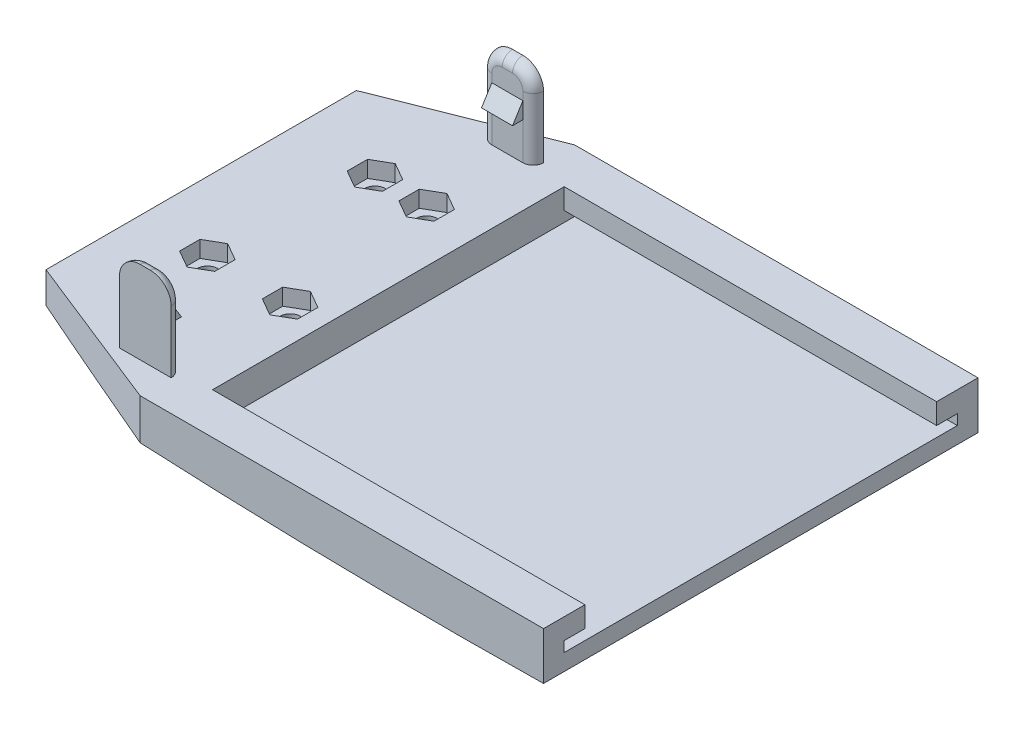
SolidWorks part; units mm, degrees
material "1060 Alloy"
ref_plane "Front Plane" through (0, 0, 0) normal (0, 0, 1) x (1, 0, 0)
ref_plane "Top Plane" through (0, 0, 0) normal (0, 1, 0) x (1, 0, 0)
ref_plane "Right Plane" through (0, 0, 0) normal (1, 0, 0) x (0, 0, -1)
sketch "Sketch1" plane through (0, 0, 0) normal (0, 1, 0) x (1, 0, 0)
  line L1 (0, 0) -> (270.5, 0)
  line L2 (0, 0) -> (0, 210)
  line L3 (0, 210) -> (270.5, 210)
  line L4 (270.5, 0) -> (270.5, 210)
  dimension "D1" = 270.5
  dimension "D2" = 210
extrude "Boss-Extrude1" add sketch "Sketch1" along normal blind 15
sketch "Sketch5" plane through (0, 15, 0) normal (0, 1, 0) x (1, 0, 0)
  line L0 (0, 105) -> (90.5, 105) construction
  line L1 (0, 210) -> (0, 0) construction
  line L3 (33, 105) -> (33, 75) construction
  line L4 (40, 105) -> (40, 149) construction
  line L5 (65, 105) -> (65, 149) construction
  line L6 (73, 105) -> (73, 75) construction
  circle A1 centre (33, 75) radius 5
  circle A2 centre (40, 149) radius 5
  circle A3 centre (65, 149) radius 5
  circle A4 centre (73, 75) radius 5
  dimension "D1" = 33
  dimension "D9" = 10
  dimension "D10" = 10
  dimension "D11" = 10
  dimension "D12" = 10
  dimension "D2" = 30
  dimension "D3" = 40
  dimension "D4" = 44
  dimension "D5" = 65
  dimension "D6" = 44
  dimension "D7" = 73
  dimension "D8" = 30
ref_plane "Plane1" through (0, 0, -150) normal (0, 0, 1) x (1, 0, 0)
sketch "Sketch12" plane through (0, 0, -150) normal (0, 0, 1) x (1, 0, 0)
  line L3 (0, 0) -> (270.5, 0) construction
  line L5 (270.5, 0) -> (270.5, -7.9767)
  line L11 (0, 0) -> (270.5, 0)
  arc A10 (0, 0) -> (270.5, -7.9767) centre (222.5, 2954.7793) ccw
  dimension "D1" = 270.5
extrude "Boss-Extrude5" add sketch "Sketch12" along normal blind 150 and the other way blind 60
extrude "Cut-Extrude7" cut sketch "Sketch5" against normal through all and the other way through all
sketch "Sketch13" plane through (0, 15, 0) normal (0, 1, 0) x (1, 0, 0)
  line L13 (40, 139.185) -> (48.5, 144.0925)
  line L14 (48.5, 144.0925) -> (48.5, 153.9075)
  line L15 (48.5, 153.9075) -> (40, 158.815)
  line L16 (40, 158.815) -> (31.5, 153.9075)
  line L17 (31.5, 153.9075) -> (31.5, 144.0925)
  line L18 (31.5, 144.0925) -> (40, 139.185)
  line L19 (73.5, 153.9075) -> (65, 158.815)
  line L20 (65, 158.815) -> (56.5, 153.9075)
  line L21 (56.5, 153.9075) -> (56.5, 144.0925)
  line L22 (56.5, 144.0925) -> (65, 139.185)
  line L23 (65, 139.185) -> (73.5, 144.0925)
  line L24 (73.5, 144.0925) -> (73.5, 153.9075)
  line L25 (33, 65.185) -> (41.5, 70.0925)
  line L26 (41.5, 70.0925) -> (41.5, 79.9075)
  line L27 (41.5, 79.9075) -> (33, 84.815)
  line L28 (33, 84.815) -> (24.5, 79.9075)
  line L29 (24.5, 79.9075) -> (24.5, 70.0925)
  line L30 (24.5, 70.0925) -> (33, 65.185)
  line L31 (73, 84.815) -> (64.5, 79.9075)
  line L32 (64.5, 79.9075) -> (64.5, 70.0925)
  line L33 (64.5, 70.0925) -> (73, 65.185)
  line L34 (73, 65.185) -> (81.5, 70.0925)
  line L35 (81.5, 70.0925) -> (81.5, 79.9075)
  line L36 (81.5, 79.9075) -> (73, 84.815)
  circle A0 centre (40, 149) radius 8.5 construction
  circle A1 centre (40, 149) radius 5 construction
  circle A2 centre (65, 149) radius 8.5 construction
  circle A3 centre (65, 149) radius 5 construction
  circle A4 centre (33, 75) radius 8.5 construction
  circle A5 centre (33, 75) radius 5 construction
  circle A6 centre (73, 75) radius 8.5 construction
  circle A7 centre (73, 75) radius 5 construction
  dimension "D1" = 17
  dimension "D2" = 17
  dimension "D3" = 17
  dimension "D4" = 17
extrude "Cut-Extrude8" cut sketch "Sketch13" against normal blind 8
sketch "Sketch15" plane through (270.5, 0, 0) normal (1, 0, 0) x (0, 0, -1)
  line L1 (20, 15) -> (190, 15)
  line L2 (10, 5) -> (10, 0)
  line L3 (10, 0) -> (200, 0)
  line L4 (200, 5) -> (200, 0)
  line L5 (0, 15) -> (0, -7.9767) construction
  line L6 (10, 5) -> (20, 5)
  line L9 (20, 5) -> (20, 15)
  line L10 (200, 5) -> (190, 5)
  line L13 (190, 5) -> (190, 15)
  dimension "D1" = 10
  dimension "D2" = 190
  dimension "D3" = 10
  dimension "D4" = 10
  dimension "D5" = 10
  dimension "D6" = 10
  dimension "D7" = 5
extrude "Cut-Extrude9" cut sketch "Sketch15" against normal blind 180
sketch "Sketch18" plane through (0, 15, 0) normal (0, 1, 0) x (1, 0, 0)
  line L0 (90.5, 190) -> (90.5, 20) construction
  line L2 (50.5, 15) -> (75.5, 15)
  line L4 (50.5, 15) -> (50.5, 20)
  line L5 (50.5, 20) -> (75.5, 20)
  line L6 (75.5, 15) -> (75.5, 20)
  line L7 (90.5, 20) -> (270.5, 20) construction
  line L8 (50.5, 190) -> (75.5, 190)
  line L9 (50.5, 190) -> (50.5, 195)
  line L10 (50.5, 195) -> (75.5, 195)
  line L11 (75.5, 190) -> (75.5, 195)
  line L12 (90.5, 190) -> (270.5, 190) construction
  dimension "D1" = 5
  dimension "D2" = 25
  dimension "D3" = 15
  dimension "D4" = 15
  dimension "D5" = 25
  dimension "D6" = 5
extrude "Boss-Extrude6" add sketch "Sketch18" along normal blind 40
sketch "Sketch19" plane through (0, 0, -20) normal (0, 0, -1) x (-1, 0, 0)
  line L0 (-75.5, 15) -> (-50.5, 15) construction
  line L1 (-55.5, 33) -> (-70.5, 33)
  line L2 (-55.5, 33) -> (-55.5, 41)
  line L3 (-55.5, 41) -> (-70.5, 41)
  line L4 (-70.5, 33) -> (-70.5, 41)
  line L5 (-50.5, 55) -> (-50.5, 15) construction
  dimension "D1" = 15
  dimension "D2" = 8
  dimension "D3" = 18
  dimension "D4" = 5
extrude "Boss-Extrude7" add sketch "Sketch19" along normal blind 5
sketch "Sketch20" plane through (55.5, 0, 0) normal (-1, 0, 0) x (0, 0, 1)
  line L0 (-20, 41) -> (-25, 33)
  line L1 (-25, 33) -> (-25, 41)
  line L2 (-25, 41) -> (-20, 41)
extrude "Cut-Extrude10" cut sketch "Sketch20" against normal up to next
fillet "Fillet1" radius 10 2 edges at (50.5, 55, -17.5) (75.5, 55, -17.5)
fillet "Fillet2" radius 5 5 edges at (50.5, 30, -20) (75.5, 30, -20) (72.5711, 52.0711, -20) (63, 55, -20) (53.4289, 52.0711, -20)
sketch "Sketch21" plane through (0, 0, -190) normal (0, 0, 1) x (1, 0, 0)
  line L0 (50.5, 15) -> (75.5, 15) construction
  line L1 (70.5, 33) -> (55.5, 33)
  line L2 (70.5, 33) -> (70.5, 41)
  line L3 (70.5, 41) -> (55.5, 41)
  line L4 (55.5, 33) -> (55.5, 41)
  line L5 (50.5, 55) -> (50.5, 15) construction
  dimension "D1" = 15
  dimension "D2" = 8
  dimension "D3" = 18
  dimension "D4" = 5
extrude "Boss-Extrude8" add sketch "Sketch21" along normal blind 5
sketch "Sketch22" plane through (55.5, 0, 0) normal (-1, 0, 0) x (0, 0, 1)
  line L0 (-185, 33) -> (-190, 41)
  line L3 (-185, 33) -> (-185, 41)
  line L4 (-185, 41) -> (-190, 41)
extrude "Cut-Extrude13" cut sketch "Sketch22" against normal up to next
fillet "Fillet3" radius 10 2 edges at (75.5, 55, -192.5) (50.5, 55, -192.5)
fillet "Fillet4" radius 5 5 edges at (75.5, 30, -190) (72.5711, 52.0711, -190) (63, 55, -190) (50.5, 30, -190) (53.4289, 52.0711, -190)
sketch "Sketch27" plane through (0, 15, 0) normal (0, 1, 0) x (1, 0, 0)
  line L0 (75.5, 210) -> (75.5, 0) construction
  line L1 (270.5, 210) -> (0, 210) construction
  line L2 (0, 0) -> (270.5, 0) construction
  line L3 (75.5, 210) -> (0, 180)
  line L4 (0, 210) -> (0, 0) construction
  line L5 (0, 180) -> (0, 210)
  line L6 (0, 210) -> (75.5, 210)
  line L7 (75.5, 0) -> (0, 30)
  line L8 (0, 30) -> (0, 0)
  line L9 (0, 0) -> (75.5, 0)
  dimension "D1" = 30
  dimension "D2" = 30
extrude "Cut-Extrude15" cut sketch "Sketch27" against normal through all
